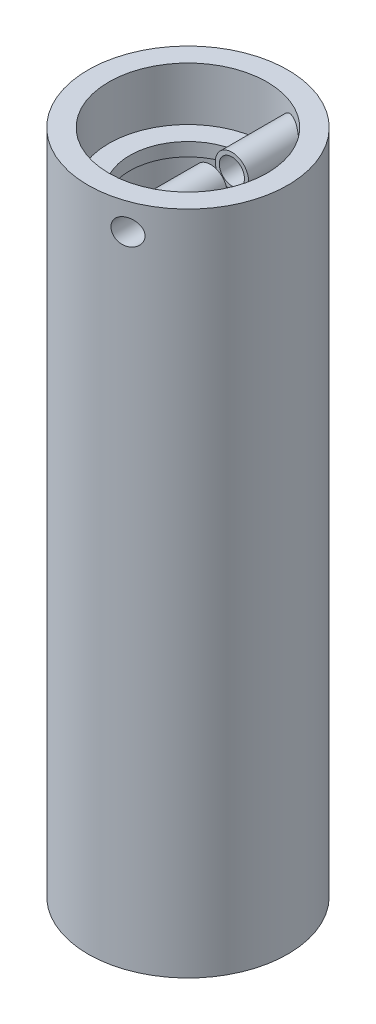
SolidWorks part; units mm, degrees
ref_plane "Front Plane" through (0, 0, 0) normal (0, 0, 1) x (1, 0, 0)
ref_plane "Top Plane" through (0, 0, 0) normal (0, 1, 0) x (1, 0, 0)
ref_plane "Right Plane" through (0, 0, 0) normal (1, 0, 0) x (0, 0, -1)
sketch "Sketch1" plane through (0, 0, 0) normal (0, 1, 0) x (1, 0, 0)
  circle A0 centre (0, 0) radius 19.05
  dimension "D1" = 38.1
extrude "Boss-Extrude1" add sketch "Sketch1" along normal mid plane 127
sketch "Sketch2" plane through (0, -63.5, 0) normal (0, -1, 0) x (1, 0, 0)
  circle A0 centre (0, 0) radius 14.2875
  dimension "D1" = 28.575
extrude "Cut-Extrude1" cut sketch "Sketch2" against normal blind 114.3
sketch "Sketch3" plane through (0, 63.5, 0) normal (0, 1, 0) x (1, 0, 0)
  circle A0 centre (0, 0) radius 11.1125
  circle A2 centre (0, 0) radius 14.2875 construction
  circle A3 centre (0, 0) radius 14.2875 construction
  dimension "D1" = 3.175
extrude "Cut-Extrude3" cut sketch "Sketch3" against normal through all
sketch "Sketch4" plane through (0, 63.5, 0) normal (0, 1, 0) x (1, 0, 0)
  line L0 (0, 11.1125) -> (0, 19.05) construction
  circle A0 centre (0, 0) radius 15.0813
  circle A1 centre (0, 0) radius 11.1125 construction
  circle A2 centre (0, 0) radius 19.05 construction
  point P10 (0, 15.0813)
extrude "Cut-Extrude5" cut sketch "Sketch4" against normal blind 10.16 and the other way through all
sketch "Sketch6" plane through (0, 0, 0) normal (0, 0, 1) x (1, 0, 0)
  line L0 (19.05, -63.5) -> (19.05, 63.5) construction
  line L1 (19.05, 63.5) -> (-19.05, 63.5) construction
  circle A0 centre (6.35, 58.42) radius 3.175
  dimension "D2" = 6.35
  dimension "D1" = 12.7
  dimension "D3" = 5.08
extrude "Boss-Extrude2" add sketch "Sketch6" along normal up to surface and the other way up to surface up to face at (0, 63.5, 15.0813) other way up to face at (0, 63.5, 15.0813)
sketch "Sketch8" plane through (0, 0, 0) normal (0, 0, 1) x (1, 0, 0)
  circle A0 centre (6.35, 58.42) radius 3.175 construction
  circle A1 centre (6.35, 58.42) radius 3.175 construction
  circle A2 centre (6.35, 58.42) radius 2.4
  dimension "D1" = 4.8
extrude "Cut-Extrude6" cut sketch "Sketch8" against normal through all both and the other way through all
sketch "Sketch9" plane through (0, 63.5, 0) normal (0, 1, 0) x (1, 0, 0)
  line L0 (3.175, 14.7433) -> (3.175, -14.7433) construction
  line L1 (3.175, -2.032) -> (9.525, -2.032)
  line L2 (3.175, -2.032) -> (3.175, 2.032)
  line L3 (3.175, 2.032) -> (9.525, 2.032)
  line L4 (9.525, -2.032) -> (9.525, 2.032)
  line L5 (3.175, -2.032) -> (9.525, 2.032) construction
  line L6 (3.175, 2.032) -> (9.525, -2.032) construction
  line L7 (9.525, -11.6927) -> (9.525, 11.6927) construction
  point P0 (6.35, 0)
  point P5 (0, 0)
  point P6 (0, 0)
  dimension "D1" = 4.064
extrude "Cut-Extrude7" cut sketch "Sketch9" against normal through all both and the other way through all
